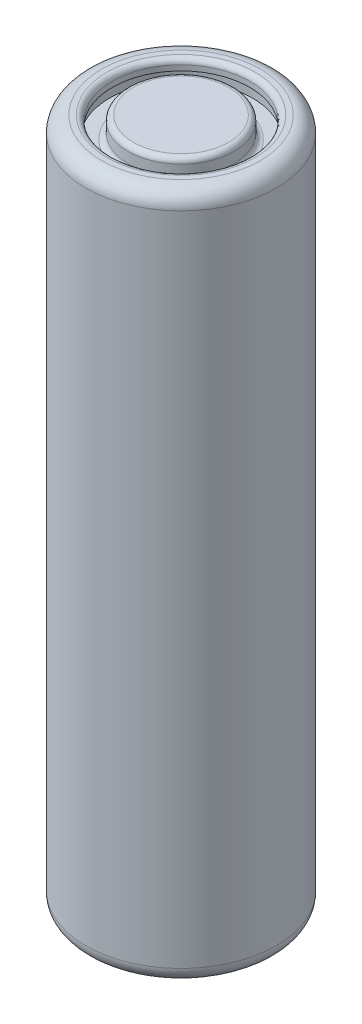
SolidWorks part; units mm, degrees
material "1023 碳钢板 (SS)"
ref_plane "前视基准面" through (0, 0, 0) normal (0, 0, 1) x (1, 0, 0)
ref_plane "上视基准面" through (0, 0, 0) normal (0, 1, 0) x (1, 0, 0)
ref_plane "右视基准面" through (0, 0, 0) normal (1, 0, 0) x (0, 0, -1)
sketch "草图1" plane through (0, 0, 0) normal (0, 1, 0) x (1, 0, 0)
  circle A0 centre (0, 0) radius 9
extrude "凸台-拉伸1" add sketch "草图1" along normal blind 65
sketch "草图2" plane through (0, 65, 0) normal (0, 1, 0) x (1, 0, 0)
  circle A0 centre (0, 0) radius 5
  circle A1 centre (0, 0) radius 6.5
extrude "切除-拉伸1" cut sketch "草图2" against normal blind 2
sketch "草图3" plane through (0, 0, 0) normal (0, -1, 0) x (-1, 0, 0)
  circle A0 centre (0, 0) radius 7.5
extrude "切除-拉伸2" cut sketch "草图3" against normal blind 0.25
sketch "草图4" plane through (0, 63, 0) normal (0, 1, 0) x (1, 0, 0)
  circle A0 centre (0, 0) radius 6.75
  circle A1 centre (0, 0) radius 5 construction
  circle A2 centre (0, 0) radius 5
extrude "切除-拉伸3" cut sketch "草图4" along normal blind 1
fillet "圆角1" radius 1.5 2 edges at (0, 0, 9) (0, 65, 9)
fillet "圆角2" radius 0.5 1 edges at (0, 65, 6.5)
fillet "圆角3" radius 0.5 2 edges at (0, 63, 5) (0, 65, 5)
